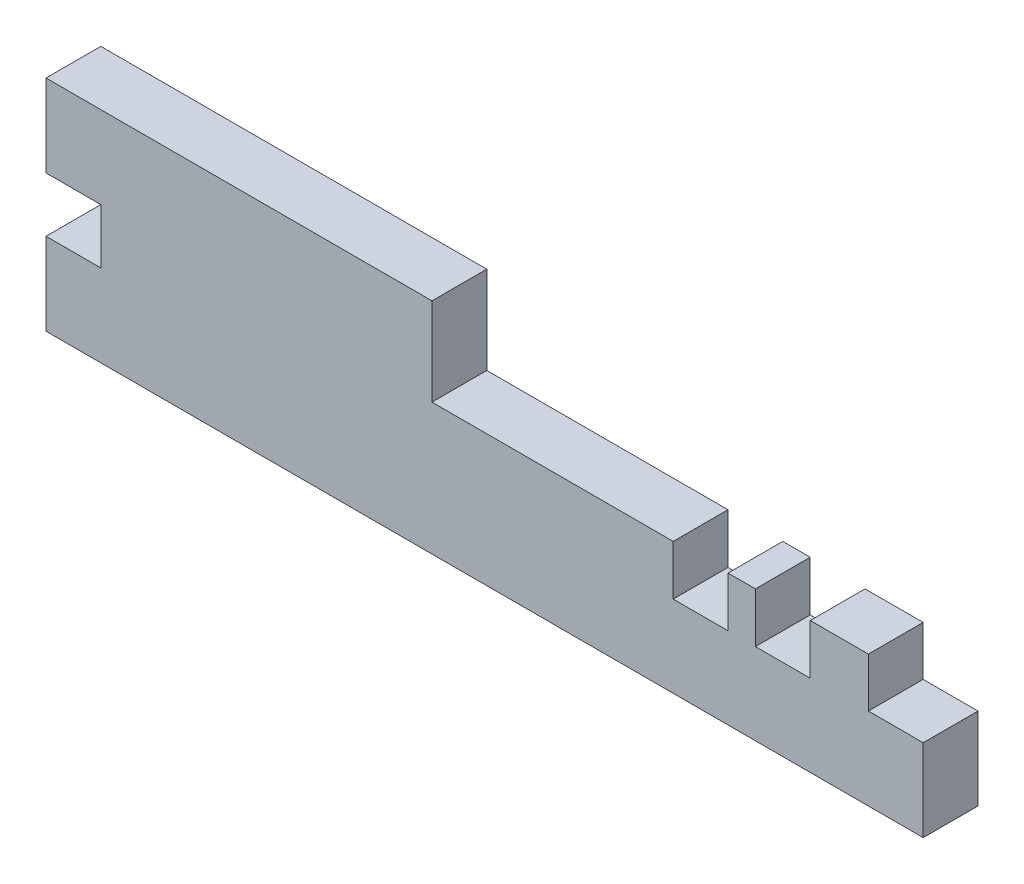
SolidWorks part; units mm, degrees
ref_plane "Plan de face" through (0, 0, 0) normal (0, 0, 1) x (1, 0, 0)
ref_plane "Plan de dessus" through (0, 0, 0) normal (0, 1, 0) x (1, 0, 0)
ref_plane "Plan de droite" through (0, 0, 0) normal (1, 0, 0) x (0, 0, -1)
sketch "Esquisse1" plane through (0, 0, 0) normal (0, 0, 1) x (1, 0, 0)
  line L0 (15.1, 0) -> (15.1, 20) construction
  line L1 (0, 0) -> (30.2, 0)
  line L2 (0, 7.5) -> (0, 12.5)
  line L3 (0, 20) -> (30.2, 20)
  line L4 (30.2, 12) -> (30.2, 20)
  line L5 (57.2, 7.4409) -> (57.2, 2.4409) construction
  line L6 (0, 20) -> (-5, 20)
  line L7 (30.2, 0) -> (70, 0)
  line L8 (0, 12.5) -> (-5, 12.5)
  line L9 (-5, 20) -> (-5, 12.5)
  line L10 (0, 0) -> (-5, 0)
  line L11 (52.2, 7.4409) -> (57.2, 7.4409)
  line L12 (0, 7.5) -> (-5, 7.5)
  line L13 (-5, 0) -> (-5, 7.5)
  line L14 (30.2, 12) -> (52.2, 12)
  line L15 (70, 7.5) -> (70, 12)
  line L16 (70, 0) -> (75, 0)
  line L17 (52.2, 7.4409) -> (52.2, 12)
  line L18 (70, 7.5) -> (75, 7.5)
  line L19 (75, 0) -> (75, 7.5)
  line L20 (64.7, 12) -> (70, 12)
  line L21 (57.2, 7.4409) -> (57.2, 12)
  line L22 (57.2, 12) -> (59.7, 12)
  line L24 (59.7, 12) -> (59.7, 7.4409)
  line L25 (59.7, 7.4409) -> (64.7, 7.4409)
  line L26 (64.7, 12) -> (64.7, 7.4409)
  dimension "D1" = 30.2
  dimension "D2" = 20
  dimension "D3" = 75
  dimension "D4" = 7.5
  dimension "D5" = 5
  dimension "D6" = 12
  dimension "D7" = 2.5
extrude "Boss.-Extru.1" add sketch "Esquisse1" along normal blind 5
